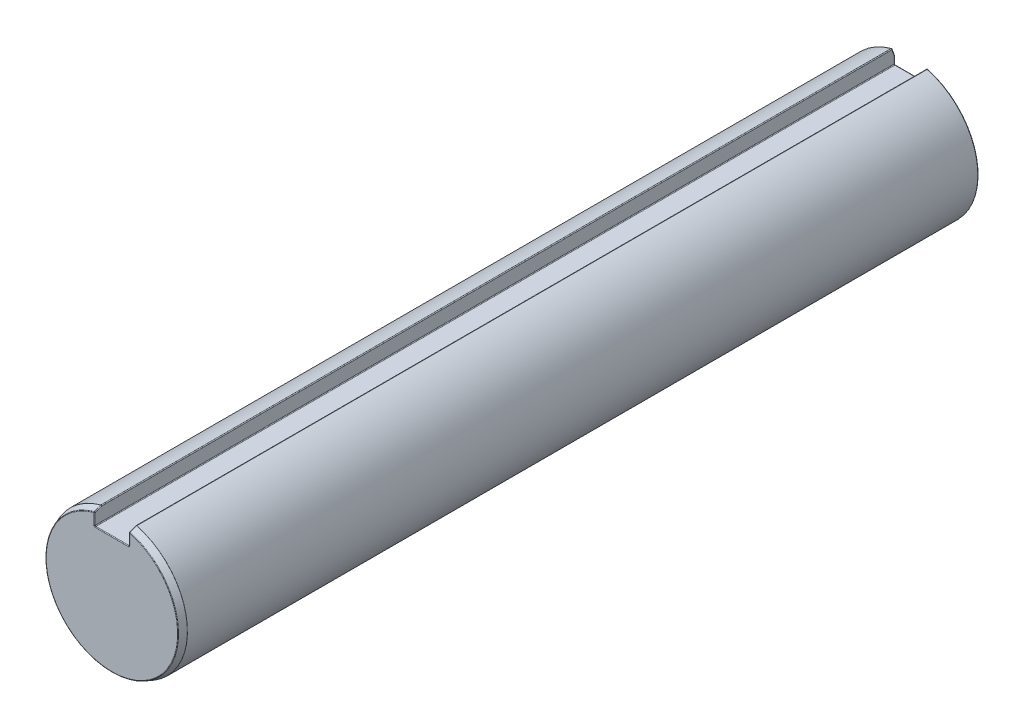
SolidWorks part; units mm, degrees
ref_plane "Front Plane" through (0, 0, 0) normal (0, 0, 1) x (1, 0, 0)
ref_plane "Top Plane" through (0, 0, 0) normal (0, 1, 0) x (1, 0, 0)
ref_plane "Right Plane" through (0, 0, 0) normal (1, 0, 0) x (0, 0, -1)
sketch "Sketch1" plane through (0, 0, 0) normal (0, 0, 1) x (1, 0, 0)
  line L1 (-1.1938, 3.5719) -> (1.1938, 3.5719)
  line L2 (-1.1938, 3.5719) -> (-1.1938, 4.7625)
  line L3 (-1.1938, 4.7625) -> (1.1938, 4.7625)
  line L4 (1.1938, 3.5719) -> (1.1938, 4.7625)
  line L5 (-1.1938, 3.5719) -> (1.1938, 4.7625) construction
  line L6 (-1.1938, 4.7625) -> (1.1938, 3.5719) construction
  circle A0 centre (0, 0) radius 4.7625
  point P3 (0, 4.1672)
  dimension "Diameter" = 9.525
  dimension "Keyway Width" = 2.3876
  dimension "Keyway Depth" = 1.1906
sketch "Sketch2" plane through (0, 0, 0) normal (1, 0, 0) x (0, 0, -1)
  line L0 (0, 4.7625) -> (0, -4.7625) construction
  line L2 (76.2, -4.7625) -> (-76.2, -4.7625)
  line L3 (76.2, -4.7625) -> (76.2, 4.7625)
  line L4 (76.2, 4.7625) -> (-76.2, 4.7625)
  line L5 (-76.2, -4.7625) -> (-76.2, 4.7625)
  line L6 (76.2, -4.7625) -> (-76.2, 4.7625) construction
  line L7 (76.2, 4.7625) -> (-76.2, -4.7625) construction
  line L8 (-76.2, -4.7625) -> (76.2, -4.7625)
  point P0 (0, 0)
  point P3 (0, 0)
  point P9 (-61.9125, -4.7625)
  point P11 (61.9125, -4.7625)
  point P15 (0, -4.7625)
  dimension "Length" = 152.4
  dimension "Keyway Length" = 152.4
  dimension "D1" = 14.2875
  dimension "D2" = 14.2875
sketch "Sketch3" plane through (0, 0, 0) normal (0, 0, 1) x (1, 0, 0)
  line L1 (-1.1938, 4.7625) -> (1.1938, 4.7625)
  line L2 (-1.1938, 4.7625) -> (-1.1938, 3.5719)
  line L3 (-1.1938, 3.5719) -> (1.1938, 3.5719)
  line L4 (1.1938, 4.7625) -> (1.1938, 3.5719)
  circle A0 centre (0, 0) radius 4.7625 construction
  circle A1 centre (0, 0) radius 4.7625
extrude "Boss-Extrude1" add sketch "Sketch3" along normal blind 27.75 and the other way blind 27.75 contours L2 A1 L4 L3 region at (0, -0.1646, 0)
chamfer "Chamfer1" distance 0.4763 angle 20 2 edges at (0, -4.7625, -27.75) (0, -4.7625, 27.75) first distance on face at (0, 1.7479, -27.75) first distance on face at (0, -0.076, 0)
fillet "Fillet1" radius 0.0476 18 edges at (0, -4.5892, 27.75) (0, -4.2863, -27.75) (0, -4.7625, -27.5767) (0, -4.7625, 27.2738) (-1.1938, 4.6104, -0.1515) (1.1938, 4.6104, -0.1515) (1.1938, 3.5719, 0) (-1.1938, 3.5719, 0) (0, 3.5719, 27.75) (1.1938, 4.0015, 27.75) (-1.1938, 4.0015, 27.75) (0, 3.5719, -27.75) (1.1938, 3.8443, -27.75) (-1.1938, 3.8443, -27.75)
equation "\"D1@Chamfer1\"=\"Diameter@Sketch1\"*.05"
equation "\"D1@Fillet1\"=\"Diameter@Sketch1\"*.005"
equation "\"D2@Sketch2\"=\"D1@Sketch2\""
equation "\"D1@Sketch2\"=\"Diameter@Sketch1\"*1.5"
